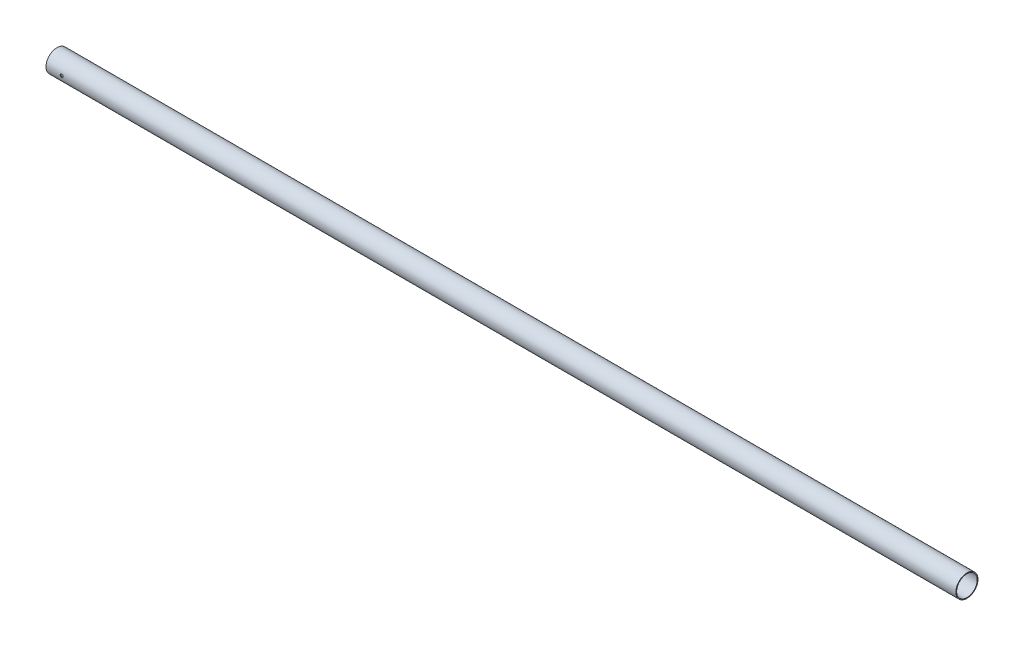
SolidWorks part; units mm, degrees
ref_plane "Front Plane" through (0, 0, 0) normal (0, 0, 1) x (1, 0, 0)
ref_plane "Top Plane" through (0, 0, 0) normal (0, 1, 0) x (1, 0, 0)
ref_plane "Right Plane" through (0, 0, 0) normal (1, 0, 0) x (0, 0, -1)
sketch "Sketch1" plane through (0, 0, 0) normal (1, 0, 0) x (0, 0, -1)
  circle A0 centre (0, 0) radius 12.7
  circle A1 centre (0, 0) radius 11.811
extrude "Boss-Extrude1" add sketch "Sketch1" along normal blind 1043.702
sketch "Sketch2" plane through (0, 0, 0) normal (0, 0, 1) x (1, 0, 0)
  circle A0 centre (18, 0) radius 1.7
extrude "Cut-Extrude1" cut sketch "Sketch2" against normal through all and the other way through all
